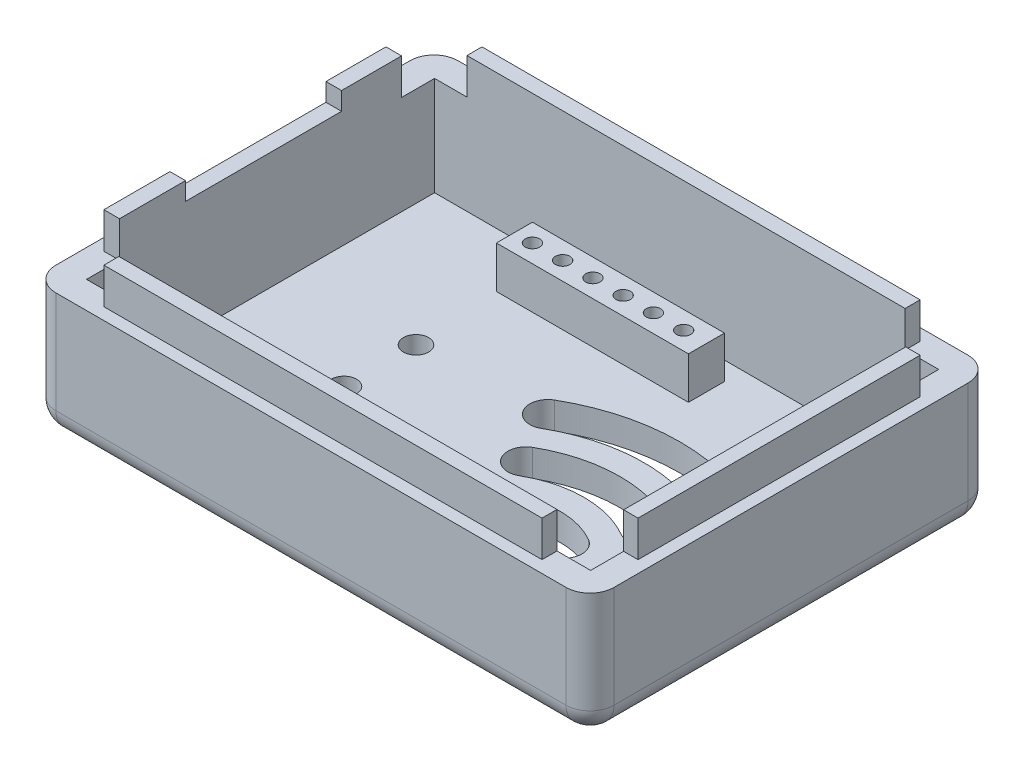
SolidWorks part; units mm, degrees
ref_plane "Front Plane" through (0, 0, 0) normal (0, 0, 1) x (1, 0, 0)
ref_plane "Top Plane" through (0, 0, 0) normal (0, 1, 0) x (1, 0, 0)
ref_plane "Right Plane" through (0, 0, 0) normal (1, 0, 0) x (0, 0, -1)
sketch "Sketch1" plane through (0, 0, 0) normal (0, 1, 0) x (1, 0, 0)
  line L5 (0, 0) -> (-46.5, 0)
  line L6 (0, 0) -> (0, 33.5)
  line L7 (0, 33.5) -> (-46.5, 33.5)
  line L8 (-46.5, 0) -> (-46.5, 33.5)
  dimension "D1" = 33.5
  dimension "D2" = 46.5
extrude "Boss-Extrude1" add sketch "Sketch1" along normal blind 13.5
sketch "Sketch2" plane through (0, 13.5, 0) normal (0, 1, 0) x (1, 0, 0)
  line L1 (-44.2, 31.25) -> (-2.2, 31.25)
  line L2 (-44.2, 31.25) -> (-44.2, 2.25)
  line L3 (-44.2, 2.25) -> (-2.2, 2.25)
  line L4 (-2.2, 31.25) -> (-2.2, 2.25)
  dimension "D1" = 42
  dimension "D2" = 2.2
  dimension "D3" = 2.25
  dimension "D4" = 29
extrude "Cut-Extrude1" cut sketch "Sketch2" against normal blind 11.25
fillet "Fillet1" radius 2 8 edges at (-46.5, 6.75, 0) (-46.5, 6.75, -33.5) (0, 6.75, -33.5) (0, 6.75, 0) (-46.5, 0, -16.75) (-23.25, 0, -33.5) (0, 0, -16.75) (-23.25, 0, 0)
sketch "Sketch3" plane through (0, 2.25, 0) normal (0, 1, 0) x (1, 0, 0)
  circle A0 centre (-34, 16.5) radius 2.5
  dimension "D2" = 5
  dimension "D1" = 16.5
  dimension "D3" = 34
sketch "Sketch4" plane through (0, 2.25, 0) normal (0, 1, 0) x (1, 0, 0)
  circle A0 centre (-34, 19.5) radius 1.05
  circle A2 centre (-34, 13.5) radius 1.05
  dimension "D2" = 2.1
  dimension "D5" = 2.1
  dimension "D1" = 19.5
  dimension "D3" = 34
  dimension "D4" = 34
  dimension "D6" = 13.5
extrude "Cut-Extrude2" cut sketch "Sketch4" against normal blind 11.25
sketch "Sketch6" plane through (0, 2.25, 0) normal (0, 1, 0) x (1, 0, 0)
  line L0 (-16, 7) -> (-28.3417, 28.3765)
  line L1 (0, -7.425) -> (0, 7.425) construction
  line L2 (-16, 7) -> (-3.5595, 28.5475)
  circle A0 centre (-16, 7) radius 1.5
  arc A4 (-18.5, 11.3301) -> (-13.5, 11.3301) centre (-16, 7) cw
  arc A5 (-21, 15.6603) -> (-11, 15.6603) centre (-16, 7) cw
  arc A6 (-23.5, 19.9904) -> (-8.5, 19.9904) centre (-16, 7) cw
  circle A7 centre (-23.5, 19.9904) radius 1.5
  circle A8 centre (-21, 15.6603) radius 1.5
  circle A9 centre (-11, 15.6603) radius 1.5
  circle A10 centre (-18.5, 11.3301) radius 1.5
  circle A11 centre (-13.5, 11.3301) radius 1.5
  circle A12 centre (-8.5, 19.9904) radius 1.5
  arc A13 (-22.75, 18.6913) -> (-9.25, 18.6913) centre (-16, 7) cw
  arc A14 (-20.25, 14.3612) -> (-11.75, 14.3612) centre (-16, 7) cw
  arc A15 (-17.75, 10.0311) -> (-14.25, 10.0311) centre (-16, 7) cw
  arc A16 (-24.25, 21.2894) -> (-7.75, 21.2894) centre (-16, 7) cw
  arc A17 (-21.75, 16.9593) -> (-10.25, 16.9593) centre (-16, 7) cw
  arc A18 (-19.25, 12.6292) -> (-12.75, 12.6292) centre (-16, 7) cw
  dimension "D3" = 3
  dimension "D4" = 5
  dimension "D5" = 10
  dimension "D6" = 15
  dimension "D7" = 30
  dimension "D15" = 3
  dimension "D16" = 3
  dimension "D17" = 3
  dimension "D18" = 3
  dimension "D19" = 3
  dimension "D20" = 3
  dimension "D1" = 16
  dimension "D2" = 7
  dimension "D8" = 0
  dimension "D9" = 0
  dimension "D10" = 0
  dimension "D11" = 30
  dimension "D12" = 0
  dimension "D13" = 0
  dimension "D14" = 0
  dimension "D21" = 1.5
  dimension "D22" = 1.5
extrude "Cut-Extrude4" cut sketch "Sketch6" against normal blind 11.25 contours A16 A7 A6 A12 | A7 A13 A12 A6 | L0 A7 A6 | A6 A7 L0 | L2 A12 A6 | A6 A12 L2 | L2 A12 | L2 A9 | L2 A11 | L2 A11 A4 | A4 A11 L2 | A5 A9 L2 | L2 A9 A5 | A17 A8 A5 A9 | A8 A14 A9 A5 | L0 A8 A5 | A5 A8 L0 | L0 A8 | L0 A7 | L0 A10 | A4 A10 L0 | L0 A10 A4 | A18 A10 A4 A11 | A10 A15 A11 A4 | L0 A0 L2 | L2 A0 L0 region at (-19.0513, 2.25, -11.0118) region at (-17.6396, 2.25, -11.047) region at (-16, 2.25, -11.1533) region at (-18.2206, 2.25, -12.1778) region at (-16, 2.25, -7.9549) region at (-16, 2.25, -6.809) region at (-16, 2.25, -12.7675) region at (-14.3604, 2.25, -11.047) region at (-12.9487, 2.25, -11.0118) region at (-21.5513, 2.25, -15.3419) region at (-20.1343, 2.25, -15.402) region at (-16, 2.25, -15.9912) region at (-13.7794, 2.25, -12.1778) region at (-20.7436, 2.25, -16.5195) region at (-16, 2.25, -17.4922) region at (-11.8657, 2.25, -15.402) region at (-10.4487, 2.25, -15.3419) region at (-24.0513, 2.25, -19.6721) region at (-22.6329, 2.25, -19.7405) region at (-16, 2.25, -20.7811) region at (-11.2564, 2.25, -16.5195) region at (-23.2513, 2.25, -20.8532) region at (-16, 2.25, -22.2562) region at (-9.3671, 2.25, -19.7405) region at (-7.9487, 2.25, -19.6721) region at (-8.7487, 2.25, -20.8532)
sketch "Sketch7" plane through (0, 2.25, 0) normal (0, 1, 0) x (1, 0, 0)
  line L0 (-46.5, 31.5) -> (-46.5, 2) construction
  circle A0 centre (-40.25, 9) radius 2
  dimension "D2" = 4
  dimension "D1" = 6.25
  dimension "D3" = 9
extrude "Cut-Extrude5" cut sketch "Sketch7" against normal blind 11.25
ref_plane "Plane1" through (0, 0, -16.75) normal (0, 0, 1) x (1, 0, 0)
sketch "Sketch8" plane through (0, 2.25, 0) normal (0, 1, 0) x (1, 0, 0)
  line L1 (-34.5, 6.8) -> (-18.5, 6.8)
  line L2 (-34.5, 6.8) -> (-34.5, 3.8)
  line L3 (-34.5, 3.8) -> (-18.5, 3.8)
  line L4 (-18.5, 6.8) -> (-18.5, 3.8)
  dimension "D1" = 18.5
  dimension "D2" = 3
  dimension "D3" = 3.8
  dimension "D4" = 16
extrude "Boss-Extrude2" add sketch "Sketch8" along normal blind 3.5
sketch "Sketch9" plane through (0, 5.75, 0) normal (0, 1, 0) x (1, 0, 0)
  circle A0 centre (-33, 5.3) radius 0.6
  point P0 (-33, 5.3)
  dimension "D3" = 1.2
  dimension "D1" = 33
  dimension "D2" = 5.3
extrude "Cut-Extrude6" cut sketch "Sketch9" against normal blind 4.5
pattern_linear "LPattern1" count 6 spacing 2.52 along (1, 0, 0) of "Cut-Extrude6"
mirror "Mirror1" about plane through (0, 0, -16.75) normal (0, 0, 1) of "LPattern1", "Cut-Extrude6", "Boss-Extrude2"
ref_axis "Axis1" through (-33, 1.25, -5.3) along (0, 1, 0)
ref_axis "Axis2" through (-33, 1.25, -28.2) along (0, 1, 0)
ref_axis "Axis3" through (-20.4, 1.25, -5.3) along (0, 1, 0)
sketch "Sketch11" plane through (0, 13.5, 0) normal (0, 1, 0) x (1, 0, 0)
  line L0 (-47.5, 34.5) -> (1, 34.5)
  line L1 (-45.5, 32.5) -> (-1, 32.5)
  line L2 (-45.5, 32.5) -> (-45.5, 1)
  line L3 (-45.5, 1) -> (-1, 1)
  line L4 (-1, 32.5) -> (-1, 1)
  line L5 (1, 34.5) -> (1, -1)
  line L6 (-47.5, -1) -> (1, -1)
  line L7 (-47.5, 34.5) -> (-47.5, -1)
  dimension "D1" = 1
  dimension "D2" = 1
  dimension "D3" = 31.5
  dimension "D4" = 44.5
  dimension "D5" = 2
extrude "Cut-Extrude7" cut sketch "Sketch11" against normal blind 3
sketch "Sketch12" plane through (0, 13.5, 0) normal (0, 1, 0) x (1, 0, 0)
  line L1 (-47, 23.5) -> (-43, 23.5)
  line L2 (-47, 23.5) -> (-47, 10.5)
  line L3 (-47, 10.5) -> (-43, 10.5)
  line L4 (-43, 23.5) -> (-43, 10.5)
  point P4 (-45, 10.5)
  dimension "D1" = 13
  dimension "D2" = 4
  dimension "D3" = 43
  dimension "D4" = 10.5
extrude "Cut-Extrude8" cut sketch "Sketch12" against normal blind 1.5
sketch "Sketch13" plane through (0, 13.5, 0) normal (0, 1, 0) x (1, 0, 0)
  line L17 (-5, 5) -> (5, 5)
  line L18 (-5, 5) -> (-5, -5)
  line L19 (-5, -5) -> (5, -5)
  line L20 (5, 5) -> (5, -5)
  line L21 (-5, 5) -> (5, -5) construction
  line L22 (-5, -5) -> (5, 5) construction
  line L23 (-5, 28.5) -> (5, 28.5)
  line L24 (-5, 28.5) -> (-5, 38.5)
  line L25 (-5, 38.5) -> (5, 38.5)
  line L26 (5, 28.5) -> (5, 38.5)
  line L27 (-5, 28.5) -> (5, 38.5) construction
  line L28 (-5, 38.5) -> (5, 28.5) construction
  line L29 (-51.5, 28.5) -> (-41.5, 28.5)
  line L30 (-51.5, 28.5) -> (-51.5, 38.5)
  line L31 (-51.5, 38.5) -> (-41.5, 38.5)
  line L32 (-41.5, 28.5) -> (-41.5, 38.5)
  line L33 (-51.5, 28.5) -> (-41.5, 38.5) construction
  line L34 (-51.5, 38.5) -> (-41.5, 28.5) construction
  line L35 (-41.5, 5) -> (-51.5, 5)
  line L36 (-41.5, 5) -> (-41.5, -5)
  line L37 (-41.5, -5) -> (-51.5, -5)
  line L38 (-51.5, 5) -> (-51.5, -5)
  line L39 (-41.5, 5) -> (-51.5, -5) construction
  line L40 (-41.5, -5) -> (-51.5, 5) construction
  point P0 (0, 0)
  point P5 (0, 33.5)
  point P10 (-46.5, 33.5)
  point P15 (-46.5, 0)
  dimension "D1" = 10
  dimension "D2" = 10
  dimension "D3" = 10
  dimension "D4" = 10
  dimension "D5" = 0
  dimension "D6" = 33.5
  dimension "D7" = 33.5
  dimension "D8" = 46.5
  dimension "D9" = 46.5
  dimension "D10" = 10
  dimension "D11" = 10
  dimension "D12" = 10
  dimension "D13" = 10
extrude "Cut-Extrude9" cut sketch "Sketch13" against normal blind 3
sketch "Sketch5" plane through (0, 2.25, 0) normal (0, 1, 0) x (1, 0, 0)
  line L1 (-40.5, 7.75) -> (-34, 7.75)
  line L2 (-40.5, 7.75) -> (-40.5, 3.25)
  line L3 (-40.5, 3.25) -> (-34, 3.25)
  line L4 (-34, 7.75) -> (-34, 3.25)
  dimension "D1" = 34
  dimension "D2" = 6.5
  dimension "D3" = 4.5
  dimension "D4" = 3.25
extrude "Cut-Extrude3" cut sketch "Sketch5" against normal blind 11.25 and the other way blind 10
fillet "Fillet2" radius 5 2 edges at (-40.5, 1.125, -7.0157) (-38.6888, 1.125, -7.75)
